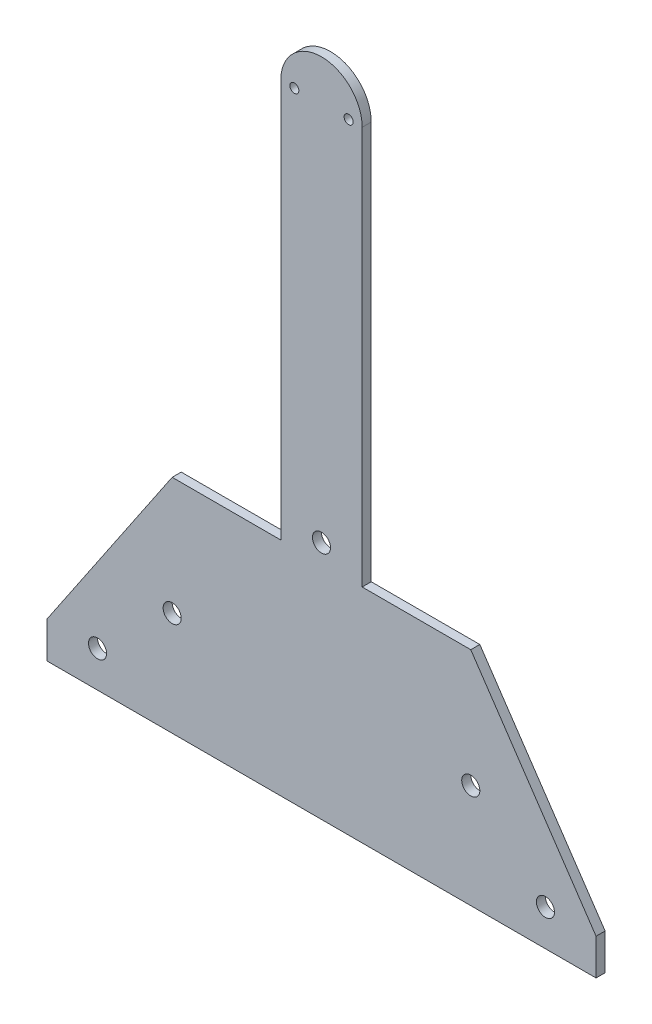
SolidWorks part; units mm, degrees
ref_plane "前视基准面" through (0, 0, 0) normal (0, 0, 1) x (1, 0, 0)
ref_plane "上视基准面" through (0, 0, 0) normal (0, 1, 0) x (1, 0, 0)
ref_plane "右视基准面" through (0, 0, 0) normal (1, 0, 0) x (0, 0, -1)
sketch "草图1" plane through (0, 0, 0) normal (0, 0, 1) x (1, 0, 0)
  line L0 (-49.7914, -7.3543) -> (-16.7914, -7.3543) construction
  line L1 (-33.2914, -7.3543) -> (-33.2914, 7.6457) construction
  line L2 (-0.2914, 7.6457) -> (-0.2914, 121.6457) construction
  line L3 (-0.2914, 121.6457) -> (5.7086, 121.6457) construction
  line L4 (-9.2914, 121.6457) -> (-9.2914, 33.6457)
  line L5 (-9.2914, 33.6457) -> (-33.2914, 33.6457)
  line L6 (-33.2914, 33.6457) -> (-60.9865, -7.3543)
  line L7 (-60.9865, -7.3543) -> (-60.9865, -15.3543)
  line L8 (-60.9865, -15.3543) -> (0, -15.3543)
  line L9 (60.4036, -15.3543) -> (-0.5829, -15.3543)
  line L10 (60.4036, -7.3543) -> (60.4036, -15.3543)
  line L11 (32.7086, 33.6457) -> (60.4036, -7.3543)
  line L12 (8.7086, 33.6457) -> (32.7086, 33.6457)
  line L13 (8.7086, 121.6457) -> (8.7086, 33.6457)
  circle A0 centre (16.2086, -7.3543) radius 2 construction
  circle A1 centre (-16.7914, -7.3543) radius 2 construction
  circle A2 centre (49.2086, -7.3543) radius 2
  circle A3 centre (-49.7914, -7.3543) radius 2
  circle A4 centre (-33.2914, 7.6457) radius 2
  circle A5 centre (32.7086, 7.6457) radius 2
  circle A6 centre (-0.2914, 7.6457) radius 2 construction
  circle A7 centre (5.7086, 121.6457) radius 1
  circle A8 centre (-6.2914, 121.6457) radius 1
  circle A9 centre (-0.2914, 121.6457) radius 1.1 construction
  circle A10 centre (-0.2914, 121.6457) radius 9 construction
  arc A11 (-9.2914, 121.6457) -> (8.7086, 121.6457) centre (-0.2914, 121.6457) cw
  circle A12 centre (-0.2914, 37.6457) radius 2
  point P37 (0, 0)
  dimension "D1" = 114
  dimension "D5" = 30
  dimension "D6" = 2
  dimension "D7" = 4
  dimension "D8" = 8
  dimension "D2" = 24
  dimension "D3" = 88
  dimension "D4" = 8
  dimension "D9" = 137
extrude "凸台-拉伸1" add sketch "草图1" along normal blind 2 contours A11 L4 L5 L6 L7 L8 L9 L10 L11 L12 L13 A9 A5 A4 A1 A0 A2 A3 A6 A7 A8 region at (-0.2914, 26.2479, 0)
